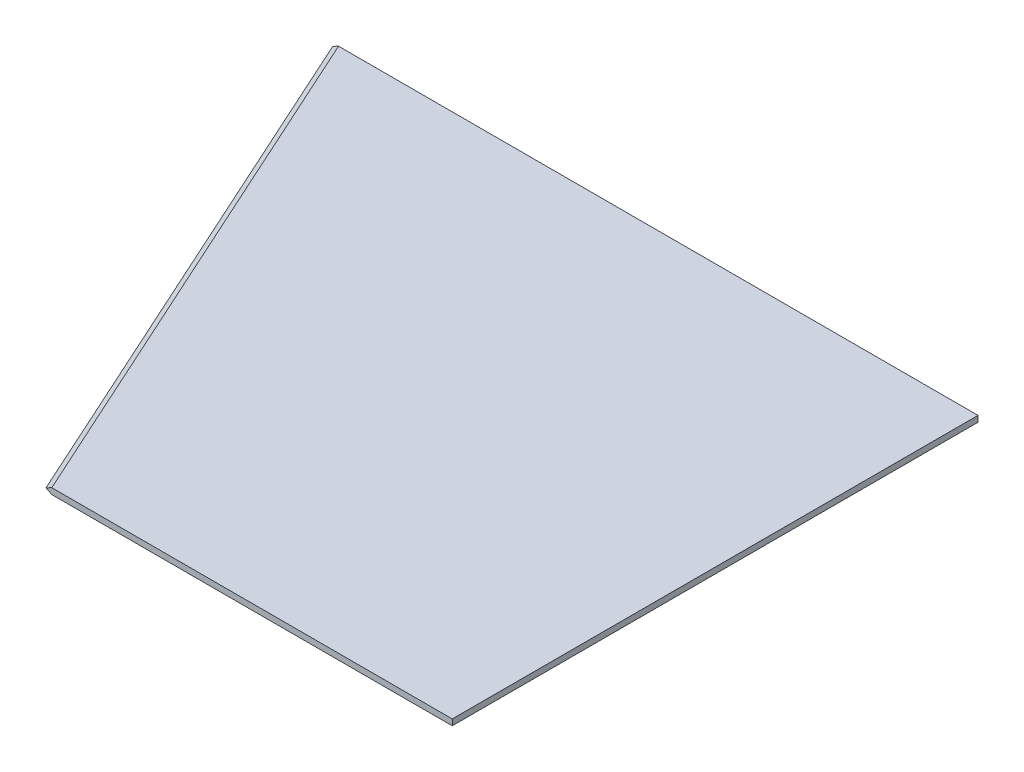
SolidWorks part; units mm, degrees
ref_plane "Front Plane" through (0, 0, 0) normal (0, 0, 1) x (1, 0, 0)
ref_plane "Top Plane" through (0, 0, 0) normal (0, 1, 0) x (1, 0, 0)
ref_plane "Right Plane" through (0, 0, 0) normal (1, 0, 0) x (0, 0, -1)
sketch "Sketch1" plane through (0, 0, 0) normal (0, 1, 0) x (1, 0, 0)
  line L0 (0, 0) -> (216, 0)
  line L1 (216, 0) -> (216, -176)
  line L2 (216, -176) -> (80, -176)
  line L3 (80, -176) -> (0, 0)
  dimension "D1" = 216
  dimension "D2" = 176
  dimension "D3" = 136
extrude "Boss-Extrude1" add sketch "Sketch1" along normal mid plane 2
chamfer "Chamfer1" distance 1.76 distance2 1 1 edges at (40, -1, 88) first distance on face at (128, -1, 88)
chamfer "Chamfer2" distance 1 distance2 1.76 1 edges at (40, 1, 88) first distance on face at (40, 0.5, 88)
